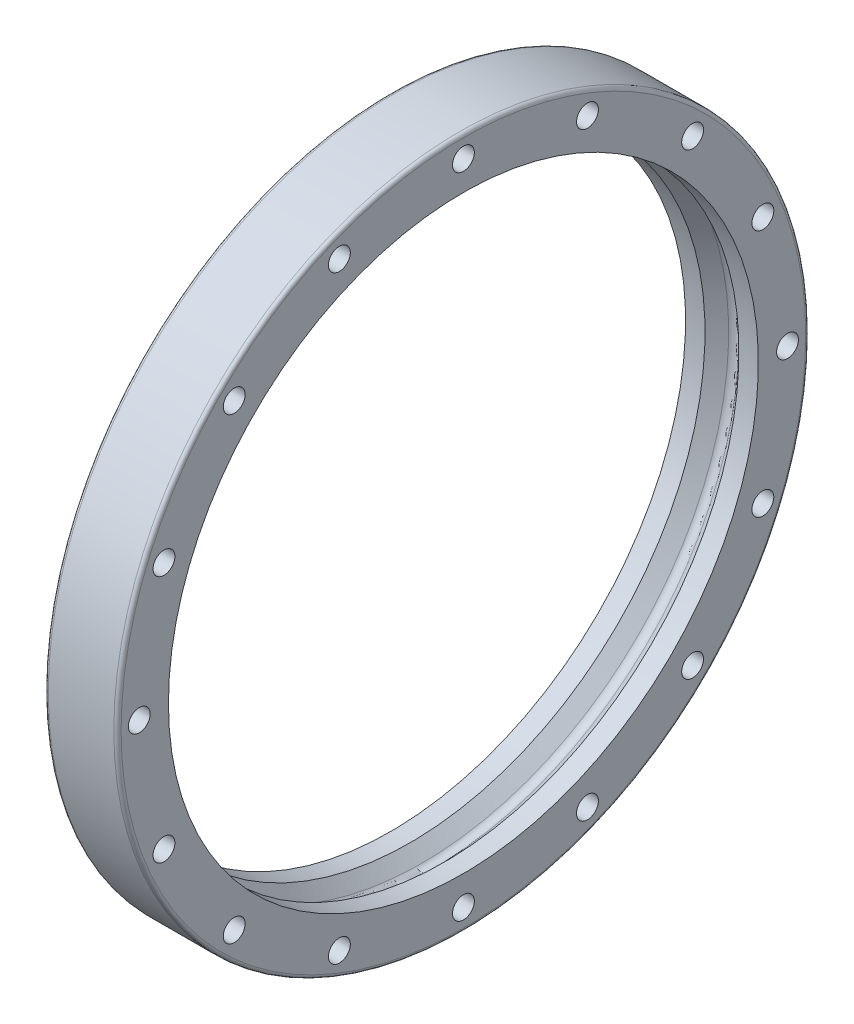
SolidWorks part; units mm, degrees
ref_plane "Front Plane" through (0, 0, 0) normal (0, 0, 1) x (1, 0, 0)
ref_plane "Top Plane" through (0, 0, 0) normal (0, 1, 0) x (1, 0, 0)
ref_plane "Right Plane" through (0, 0, 0) normal (1, 0, 0) x (0, 0, -1)
sketch "Sketch1" plane through (0, 0, 0) normal (0, 0, 1) x (1, 0, 0)
  line L0 (-42.0673, 0) -> (0, 0) construction
  line L1 (0, 0) -> (0, 88) construction
  line L2 (0, 85.6569) -> (5.6569, 80)
  line L3 (10, 95) -> (-10, 95)
  line L4 (10, 95) -> (10, 81)
  line L5 (10, 81) -> (-10, 81)
  line L6 (-10, 95) -> (-10, 81)
  line L7 (10, 95) -> (-10, 81) construction
  line L8 (10, 81) -> (-10, 95) construction
  line L9 (10, 79) -> (-10, 79)
  line L10 (10, 79) -> (10, 65)
  line L11 (10, 65) -> (-10, 65)
  line L12 (-10, 79) -> (-10, 65)
  line L13 (10, 79) -> (-10, 65) construction
  line L14 (10, 65) -> (-10, 79) construction
  line L15 (0, 85.6569) -> (-5.6569, 80)
  line L16 (5.6569, 80) -> (0, 74.3431)
  line L17 (-5.6569, 80) -> (0, 74.3431)
  line L18 (0, 85.6569) -> (0, 74.3431) construction
  line L19 (5.6569, 80) -> (-5.6569, 80) construction
  point P8 (0, 72)
  point P14 (0, 80)
  dimension "D1" = 20
  dimension "D2" = 65
  dimension "D3" = 95
  dimension "D4" = 14
  dimension "D5" = 1
  dimension "D6" = 8
revolve "Revolve1" add sketch "Sketch1" angle 360 about L0 region at (0, 88.4574, 0)
ref_axis "Axis1" through (10, 0, 0) along (-1, 0, 0)
fillet "Fillet1" radius 2 1 edges at (0, 0, 85.6569)
sketch "Sketch2" plane through (10, 0, 0) normal (1, 0, 0) x (0, 0, -1)
  circle A0 centre (0, 0) radius 89 construction
  circle A1 centre (0, 89) radius 3
  point P5 (0, 0)
  dimension "D1" = 6
  dimension "D2" = 178
extrude "Cut-Extrude1" cut sketch "Sketch2" against normal through all
pattern_circular "CirPattern1" count 16 over 360 about axis through (10, 0, 0) along (-1, 0, 0) of "Cut-Extrude1"
fillet "Fillet2" radius 1 2 edges at (10, 0, 95) (-10, 0, 95)
